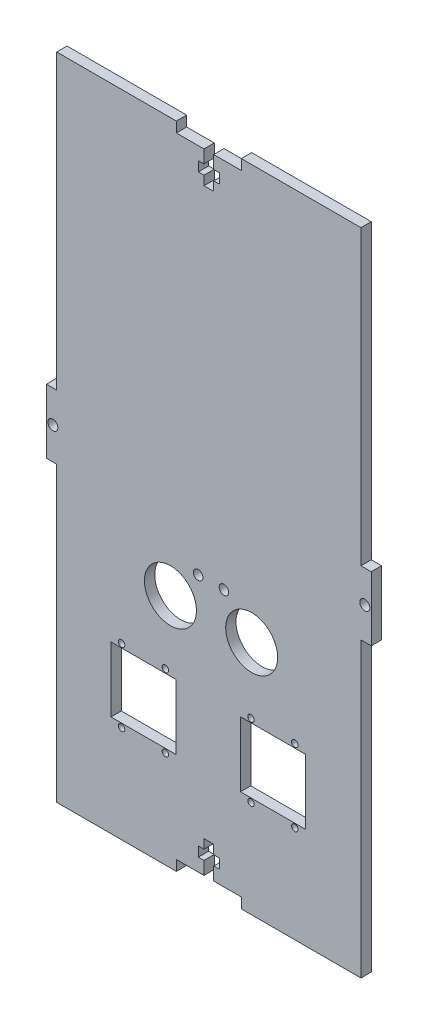
SolidWorks part; units mm, degrees
ref_plane "Front Plane" through (0, 0, 0) normal (0, 0, 1) x (1, 0, 0)
ref_plane "Top Plane" through (0, 0, 0) normal (0, 1, 0) x (1, 0, 0)
ref_plane "Right Plane" through (0, 0, 0) normal (1, 0, 0) x (0, 0, -1)
sketch "Sketch1" plane through (0, 0, 0) normal (0, 0, 1) x (1, 0, 0)
  line L0 (0.1756, 148.1163) -> (0.1756, -143.3274) construction
  line L5 (-50, -100) -> (50, 100) construction
  line L6 (-50, 100) -> (50, -100) construction
  line L7 (-100, 0) -> (100, 0) construction
  line L32 (-50, 100) -> (50, 100)
  line L35 (50, 100) -> (50, -100)
  line L36 (50, -100) -> (-50, -100)
  line L37 (-50, -100) -> (-50, 100)
  point P0 (0, 0)
  dimension "D1" = 100
  dimension "D2" = 200
extrude "Boss-Extrude2" add sketch "Sketch1" along normal blind 3.18
sketch "Sketch2" plane through (0, 0, 3.18) normal (0, 0, 1) x (1, 0, 0)
  line L0 (0, -100) -> (0, 100) construction
  line L1 (-123.0225, 0) -> (147.0753, 0) construction
  line L2 (50, 100) -> (-50, 100) construction
  line L4 (-10, 100) -> (-10, 96.82)
  line L5 (-10, 96.82) -> (-1.5, 96.82)
  line L6 (10, 100) -> (10, 96.82)
  line L7 (1.5, 96.82) -> (10, 96.82)
  line L9 (-1.5, 96.82) -> (-1.5, 92.82)
  line L10 (-1.5, 87) -> (1.5, 87)
  line L11 (1.5, 96.82) -> (1.5, 92.82)
  line L12 (-3.25, 92.82) -> (-1.5, 92.82)
  line L13 (-3.25, 92.82) -> (-3.25, 89.82)
  line L14 (-3.25, 89.82) -> (-1.5, 89.82)
  line L15 (3.25, 92.82) -> (3.25, 89.82)
  line L16 (1.5, 92.82) -> (3.25, 92.82)
  line L17 (-1.5, 89.82) -> (-1.5, 87)
  line L18 (1.5, 89.82) -> (1.5, 87)
  line L19 (1.5, 89.82) -> (3.25, 89.82)
  line L20 (-10, 100) -> (10, 100)
  line L21 (-50, -100) -> (50, -100) construction
  line L22 (-50, 100) -> (-50, -100) construction
  line L23 (-50, 9.875) -> (-46.82, 9.875)
  line L24 (-50, 9.875) -> (-50, 100)
  line L25 (-50, 100) -> (-46.82, 100)
  line L26 (-46.82, 9.875) -> (-46.82, 100)
  line L28 (-50, -9.875) -> (-46.82, -9.875)
  line L29 (-50, -9.875) -> (-50, -100)
  line L30 (-50, -100) -> (-46.82, -100)
  line L31 (-46.82, -9.875) -> (-46.82, -100)
  circle A0 centre (-48, 0) radius 1.55
  dimension "D11" = 3.1
  dimension "D12" = 2
  dimension "D1" = 4
  dimension "D2" = 3
  dimension "D3" = 3
  dimension "D4" = 20
  dimension "D5" = 6.5
  dimension "D6" = 3.18
  dimension "D7" = 13
  dimension "D8" = 19.75
  dimension "D9" = 3.18
  dimension "D10" = 3.18
extrude "Cut-Extrude1" cut sketch "Sketch2" against normal through all
mirror "Mirror1" about plane through (0, 0, 0) normal (0, 1, 0) of "Cut-Extrude1"
mirror "Mirror3" about plane through (0, 0, 0) normal (1, 0, 0) of "Cut-Extrude1"
sketch "Sketch4" plane through (0, 0, 0) normal (0, 0, -1) x (-1, 0, 0)
  circle A1 centre (13.3617, -70.1191) radius 1
  circle A2 centre (13.3617, -70.1191) radius 0.975 construction
  circle A3 centre (26.8617, -70.1191) radius 1
  circle A7 centre (26.8617, -70.1191) radius 0.975 construction
  circle A8 centre (26.8617, -47.6591) radius 1
  circle A9 centre (26.8617, -47.6591) radius 0.975 construction
  circle A10 centre (13.3617, -47.6591) radius 1
  circle A11 centre (13.3617, -47.6591) radius 0.975 construction
  circle A12 centre (-12.9789, -47.6824) radius 1
  circle A13 centre (-26.4789, -47.6824) radius 1
  circle A14 centre (-26.4789, -70.1424) radius 1
  circle A15 centre (-12.9789, -70.1424) radius 1
  circle A16 centre (-26.4789, -70.1424) radius 0.975 construction
  circle A17 centre (-12.9789, -70.1424) radius 0.975 construction
  circle A18 centre (-26.4789, -47.6824) radius 0.975 construction
  circle A19 centre (-12.9789, -47.6824) radius 0.975 construction
  dimension "D2" = 2
extrude "Cut-Extrude15" cut sketch "Sketch4" against normal blind 10
sketch "Sketch5" plane through (0, 0, 0) normal (0, 0, -1) x (-1, 0, 0)
  circle A0 centre (11.82, -27.4214) radius 8
  circle A1 centre (-13.18, -27.4214) radius 8
  circle A2 centre (11.82, -27.4214) radius 8 construction
  circle A3 centre (-13.18, -27.4214) radius 8 construction
  dimension "D1" = 16
extrude "Cut-Extrude16" cut sketch "Sketch5" against normal through all
sketch "Sketch6" plane through (0, 0, 0) normal (0, 0, -1) x (-1, 0, 0)
  circle A0 centre (3.2835, -17.6169) radius 1.47
  circle A2 centre (-4.6435, -17.6169) radius 1.47
  circle A3 centre (3.2835, -17.6169) radius 1.47 construction
  circle A4 centre (-4.6435, -17.6169) radius 1.47 construction
extrude "Cut-Extrude17" cut sketch "Sketch6" against normal through all
sketch "Sketch7" plane through (0, 0, 0) normal (0, 0, -1) x (-1, 0, 0)
  line L1 (30.1117, -48.8891) -> (10.1117, -48.8891)
  line L2 (30.1117, -48.8891) -> (30.1117, -68.8891)
  line L3 (30.1117, -68.8891) -> (10.1117, -68.8891)
  line L4 (10.1117, -48.8891) -> (10.1117, -68.8891)
  line L5 (-9.7289, -48.9124) -> (-29.7289, -48.9124)
  line L6 (-9.7289, -48.9124) -> (-9.7289, -68.9124)
  line L7 (-9.7289, -68.9124) -> (-29.7289, -68.9124)
  line L8 (-29.7289, -48.9124) -> (-29.7289, -68.9124)
  dimension "D1" = 20
extrude "Cut-Extrude18" cut sketch "Sketch7" against normal through all contours L2 L1 L4 L3 | L6 L5 L8 L7
